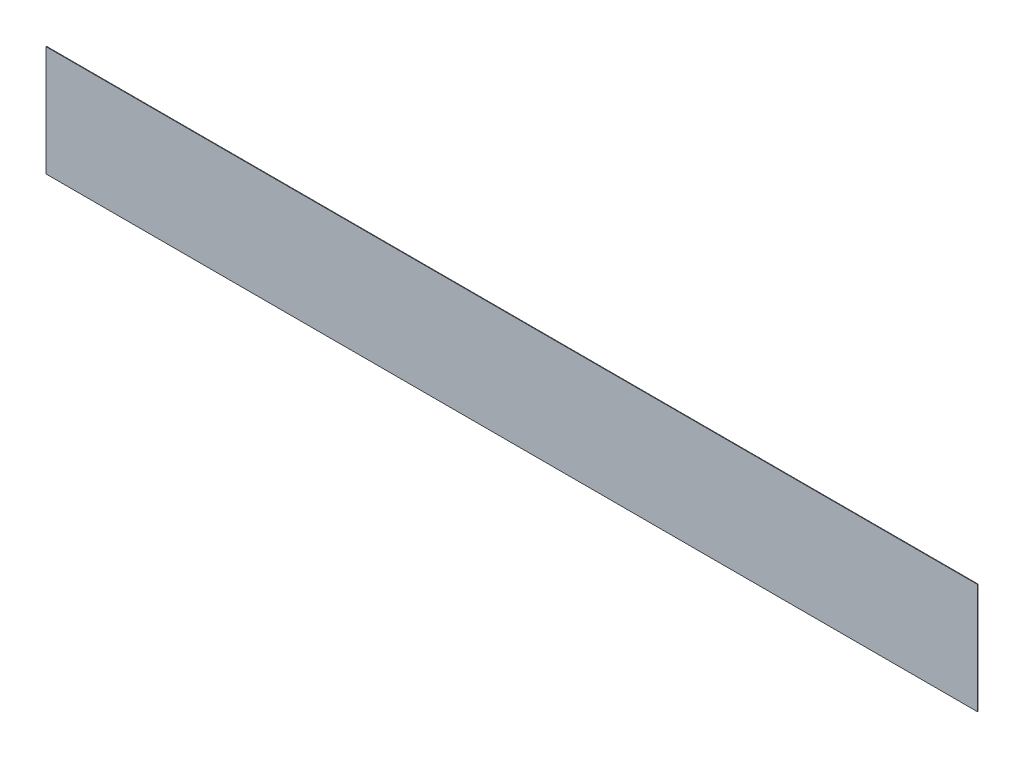
SolidWorks part; units mm, degrees
ref_plane "前视基准面" through (0, 0, 0) normal (0, 0, 1) x (1, 0, 0)
ref_plane "上视基准面" through (0, 0, 0) normal (0, 1, 0) x (1, 0, 0)
ref_plane "右视基准面" through (0, 0, 0) normal (1, 0, 0) x (0, 0, -1)
sketch "草图1" plane through (0, 0, 0) normal (0, 0, 1) x (1, 0, 0)
  line L1 (-650.25, 77) -> (650.25, 77)
  line L2 (-650.25, 77) -> (-650.25, -77)
  line L3 (-650.25, -77) -> (650.25, -77)
  line L4 (650.25, 77) -> (650.25, -77)
  line L5 (-650.25, 77) -> (650.25, -77) construction
  line L6 (-650.25, -77) -> (650.25, 77) construction
  point P0 (0, 0)
  dimension "D1" = 1300.5
  dimension "D2" = 154
base flange "基体-法兰1" sketch "草图1" thickness 0.8 reverse thickness direction no parameters "D1"=0.5
sketch "折弯-线1" plane through (0, 0, 0) normal (0, 1, 0) x (1, 0, 0)
sketch "边界框1" plane through (0, 0, 0) normal (0, 1, 0) x (1, 0, 0)
sheet metal parameters "钣金1" thickness 0.8 parameters "D1"=0.5
flat pattern "平板型式1" [suppressed]
sketch "折弯-线2" plane through (0, 0, 0) normal (0, 1, 0) x (1, 0, 0)
sketch "边界框2" [suppressed] plane through (0, 0, 0) normal (0, 1, 0) x (1, 0, 0)
